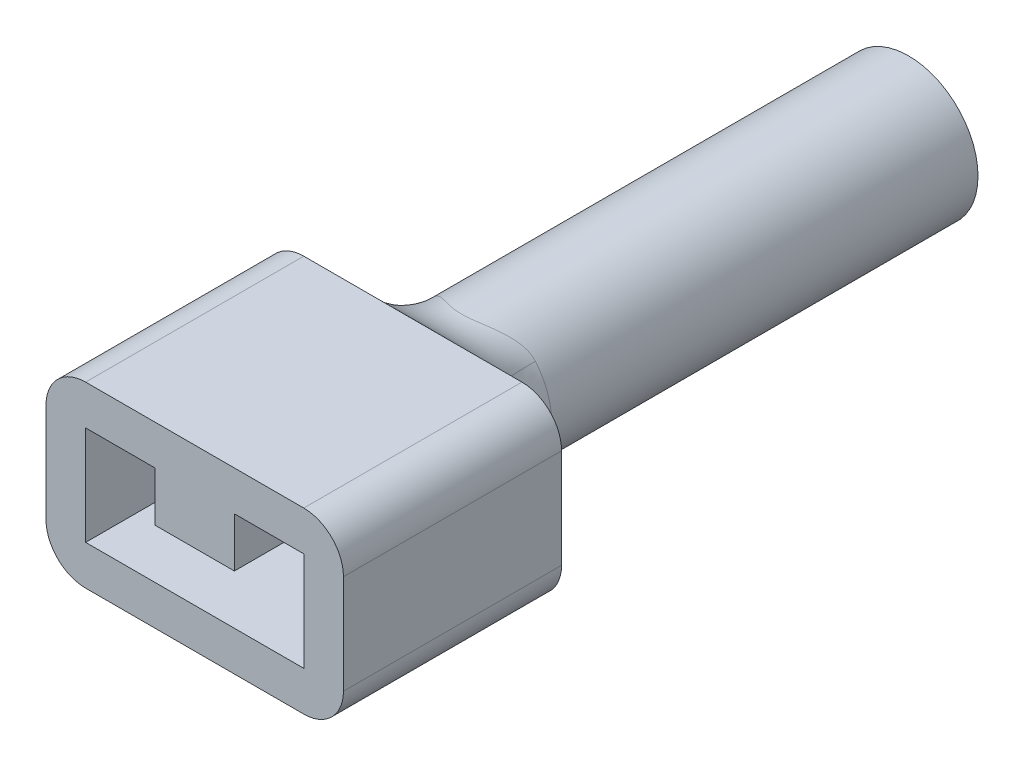
SolidWorks part; units mm, degrees
ref_plane "Front Plane" through (0, 0, 0) normal (0, 0, 1) x (1, 0, 0)
ref_plane "Top Plane" through (0, 0, 0) normal (0, 1, 0) x (1, 0, 0)
ref_plane "Right Plane" through (0, 0, 0) normal (1, 0, 0) x (0, 0, -1)
sketch "Sketch2" plane through (0, 0, 0) normal (0, 0, 1) x (1, 0, 0)
  line L0 (-1.2374, -1.2374) -> (1.2374, -1.2374)
  arc A0 (1.2374, -1.2374) -> (-1.2374, -1.2374) centre (0, 0) ccw
  circle A1 centre (0, 0) radius 3.5
  dimension "D1" = 3.5
  dimension "D2" = 7
extrude "Boss-Extrude1" add sketch "Sketch2" along normal blind 8
sketch "Sketch3" plane through (0, 0, 8) normal (0, 0, 1) x (1, 0, 0)
  circle A0 centre (0, 0) radius 3.5
extrude "Boss-Extrude2" add sketch "Sketch3" along normal blind 18
sketch "Sketch4" plane through (0, 0, 26) normal (0, 0, 1) x (1, 0, 0)
  line L0 (-7.5, -4.5) -> (-7.5, 4.5)
  line L1 (-5.5, -2.5) -> (5.5, -2.5)
  line L2 (-5.5, -2.5) -> (-5.5, 2.5)
  line L3 (0, 0) -> (0, 4.5) construction
  line L4 (5.5, -2.5) -> (5.5, 2.5)
  line L5 (-5.5, -2.5) -> (5.5, 2.5) construction
  line L6 (-5.5, 2.5) -> (5.5, -2.5) construction
  line L7 (-7.5, 4.5) -> (7.5, 4.5)
  line L8 (7.5, -4.5) -> (7.5, 4.5)
  line L9 (-7.5, -4.5) -> (7.5, -4.5)
  line L10 (-5.5, 2.5) -> (5.5, 2.5) construction
  line L11 (0, 2.5) -> (-2, 2.5) construction
  line L12 (0, 2.5) -> (2, 2.5) construction
  line L13 (2, 2.5) -> (2, 0)
  line L14 (2, 0) -> (-2, 0)
  line L15 (-2, 0) -> (-2, 2.5)
  line L16 (2, 2.5) -> (5.5, 2.5)
  line L17 (-2, 2.5) -> (-5.5, 2.5)
  point P0 (0, 0)
  dimension "D1" = 11
  dimension "D2" = 5
  dimension "D4" = 2
  dimension "D5" = 2
  dimension "D6" = 2.5
  dimension "D3" = 2
extrude "Boss-Extrude3" add sketch "Sketch4" along normal blind 10
sketch "Sketch5" plane through (0, 0, 26) normal (0, 0, -1) x (-1, 0, 0)
  line L1 (7.5, 4.5) -> (-7.5, 4.5)
  line L2 (7.5, 4.5) -> (7.5, -4.5)
  line L3 (7.5, -4.5) -> (-7.5, -4.5)
  line L4 (-7.5, 4.5) -> (-7.5, -4.5)
extrude "Boss-Extrude4" add sketch "Sketch5" along normal blind 1
fillet "Fillet1" radius 3.5 1 edges at (3.5, 0, 25)
fillet "Fillet2" radius 2 4 edges at (7.5, 4.5, 30.5) (-7.5, -4.5, 30.5) (7.5, -4.5, 30.5) (-7.5, 4.5, 30.5)
